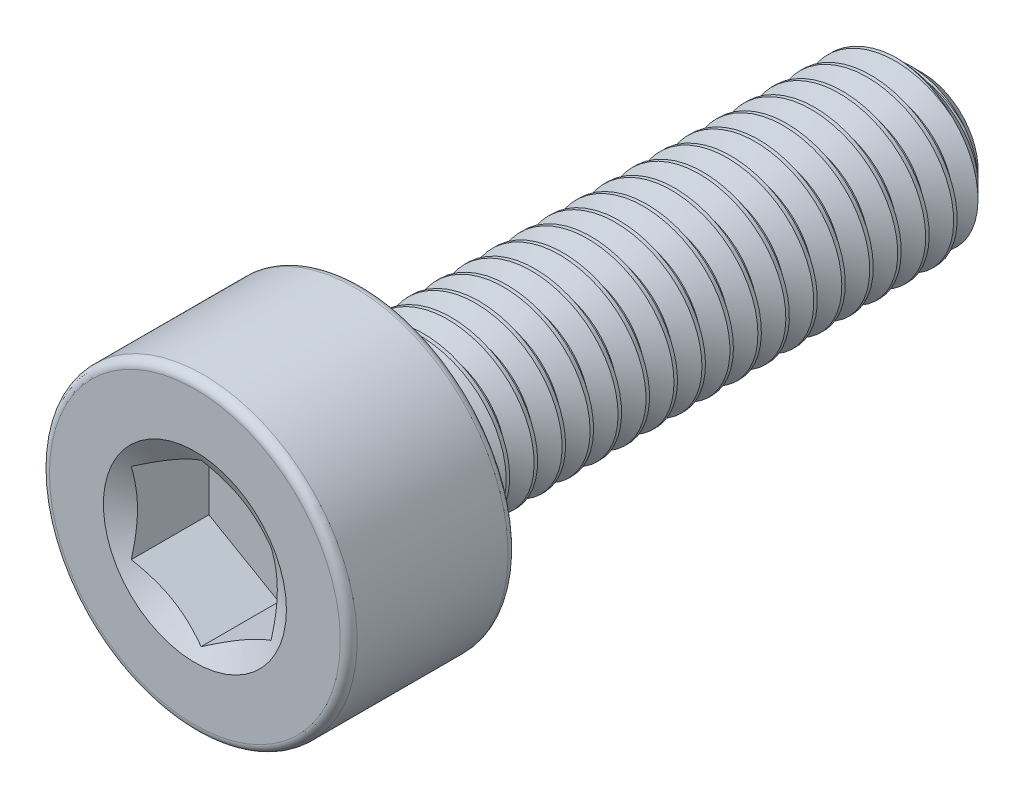
SolidWorks part; units mm, degrees
ref_plane "Front Plane" through (0, 0, 0) normal (0, 0, 1) x (1, 0, 0)
ref_plane "Top Plane" through (0, 0, 0) normal (0, 1, 0) x (1, 0, 0)
ref_plane "Right Plane" through (0, 0, 0) normal (1, 0, 0) x (0, 0, -1)
sketch "Sketch1" plane through (0, 0, 0) normal (1, 0, 0) x (0, 0, -1)
  line L0 (6.5, 0) -> (-6.5, 0) construction
  line L1 (-3.5, 2.75) -> (-3.5, -2.75) construction
  line L2 (6.5, 1.5) -> (6.5, -1.5) construction
  line L3 (6.4688, 1.5541) -> (6.7188, 1.1211) construction
  line L4 (6.6875, 1.1752) -> (6.75, 1.1752) construction
  line L5 (6.7188, 1.1211) -> (6.9688, 1.5541) construction
  line L6 (6.9688, 1.5541) -> (6.4688, 1.5541) construction
  line L7 (6.7188, 1.1752) -> (6.7188, 1.1211) construction
  line L8 (6.7188, 1.5541) -> (6.7188, 1.5) construction
  line L9 (6.9375, 1.5) -> (6.5, 1.5) construction
  point P4 (-3.5, 0)
  point P6 (-3.5, 1.25)
  point P7 (5.25, -1.5)
  point P20 (6.7188, 1.5271)
  dimension "Head Height" = 3
  dimension "Head Diameter" = 5.5
  dimension "Drive Size" = 2.5
  dimension "Length" = 10
  dimension "Thread Size" = 3
  dimension "Thread Pitch" = 0.5
  dimension "Pitch/8" = 0.0625
  dimension "Thread Note" = 1.25
sketch "Sketch2" plane through (0, 0, 0) normal (1, 0, 0) x (0, 0, -1)
  line L0 (6.5, 0) -> (6.5, 1)
  line L1 (6.5, 1.5) -> (6.5, -1.5) construction
  line L2 (6.5, 1) -> (6, 1.5)
  line L3 (6, 1.5) -> (-3.5, 1.5)
  line L4 (-3.5, 1.5) -> (-3.5, 2.6)
  line L5 (-3.65, 2.75) -> (-6.35, 2.75)
  line L6 (-6.5, 2.6) -> (-6.5, 0)
  line L7 (6.5, 0) -> (-6.5, 0) construction
  line L8 (-6.5, 0) -> (6.5, 0)
  arc A0 (-3.5, 2.6) -> (-3.65, 2.75) centre (-3.65, 2.6) ccw
  arc A1 (-6.35, 2.75) -> (-6.5, 2.6) centre (-6.35, 2.6) ccw
  point P19 (-3.5, 2.75)
  dimension "D3" = 0.15
  dimension "D1" = 0.5
  dimension "D2" = 45
revolve "Revolve1" add sketch "Sketch2" angle 360 about L0
sketch "Sketch3" plane through (0, 0, 0) normal (0, 0, 1) x (1, 0, 0)
  line L1 (-1.25, 0.7217) -> (-1.25, -0.7217)
  line L2 (-1.25, -0.7217) -> (0, -1.4434)
  line L3 (0, -1.4434) -> (1.25, -0.7217)
  line L4 (1.25, -0.7217) -> (1.25, 0.7217)
  line L5 (1.25, 0.7217) -> (0, 1.4434)
  line L6 (0, 1.4434) -> (-1.25, 0.7217)
  circle A0 centre (0, 0) radius 1.25 construction
  circle A1 centre (0, 0) radius 2.75 construction
extrude "Cut-Extrude1" cut sketch "Sketch3" against normal blind 1.5 from vertex starting at point (0, 0, 6.5)
sketch "Sketch4" plane through (0, 0, 6.5) normal (0, 0, 1) x (1, 0, 0)
  line L0 (0, 1.4434) -> (0, 1.8289) construction
  line L1 (0, 1.8289) -> (0, 2.2145) construction
  line L2 (0, 2.2145) -> (0, 2.6) construction
  circle A0 centre (0, 0) radius 1.6361
  point P12 (0, 1.6361)
extrude "Cut-Extrude2" cut sketch "Sketch4" against normal through all draft 60
split "Split1" bodies to split 106 112 resulting bodies 107 108 split by face at (-2.6, 0, 3.5)
sketch "Sketch5" plane through (0, 0, 0) normal (1, 0, 0) x (0, 0, -1)
  line L0 (6.6875, 1.1752) -> (6.75, 1.1752)
  line L1 (6.75, 1.1752) -> (6.9531, 1.5271)
  line L2 (6.9531, 1.5271) -> (6.4844, 1.5271)
  line L3 (6.4844, 1.5271) -> (6.6875, 1.1752)
  line L4 (6.4688, 1.5541) -> (6.7188, 1.1211) construction
sketch "Sketch6" plane through (0, 0, -6.5) normal (0, 0, -1) x (-1, 0, 0)
  circle A0 centre (0, 0) radius 1.5
curve "Helix/Spiral1" pitch 0.5 height 10.5 radius 1.5 centre (0, 0, -6.5) axis (0, 0, 1) start towards (0, 1, 0)
sweep "Cut-Sweep1" cut profiles "Sketch5" path "Helix/Spiral1" align with end faces yes
sketch "Sketch7" plane through (0, 0, 3.5) normal (0, 0, -1) x (-1, 0, 0)
  circle A0 centre (0, 0) radius 1.5508
  circle A1 centre (0, 0) radius 1.5 construction
  dimension "D1" = 0.0508
extrude "Boss-Extrude1" add sketch "Sketch7" along normal blind 1.5 draft 20 and the other way blind 0.3
equation "\"Pitch/8@Sketch1\" = \"Thread Pitch@Sketch1\" / 8"
equation "\"Thread Note@Sketch1\" = \"Thread Pitch@Sketch1\" * 2.5"
equation "\"D1@Sketch2\" = \"Thread Pitch@Sketch1\""
equation "\"D3@Sketch2\"=\"Head Height@Sketch1\"*.05"
equation "\"D1@Cut-Extrude1\" = \"Head Height@Sketch1\" * .5"
equation "\"D3@Helix/Spiral1\" = \"Length@Sketch1\" + \"Thread Pitch@Sketch1\""
equation "\"D4@Helix/Spiral1\" = \"Thread Pitch@Sketch1\""
equation "\"D2@Boss-Extrude1\" = \"Head Height@Sketch1\" * .1"
equation "\"D1\"= \"Thread Size@Sketch1\" * .4"
equation "\"D1@Boss-Extrude1\" = \"Thread Pitch@Sketch1\" * 3"
